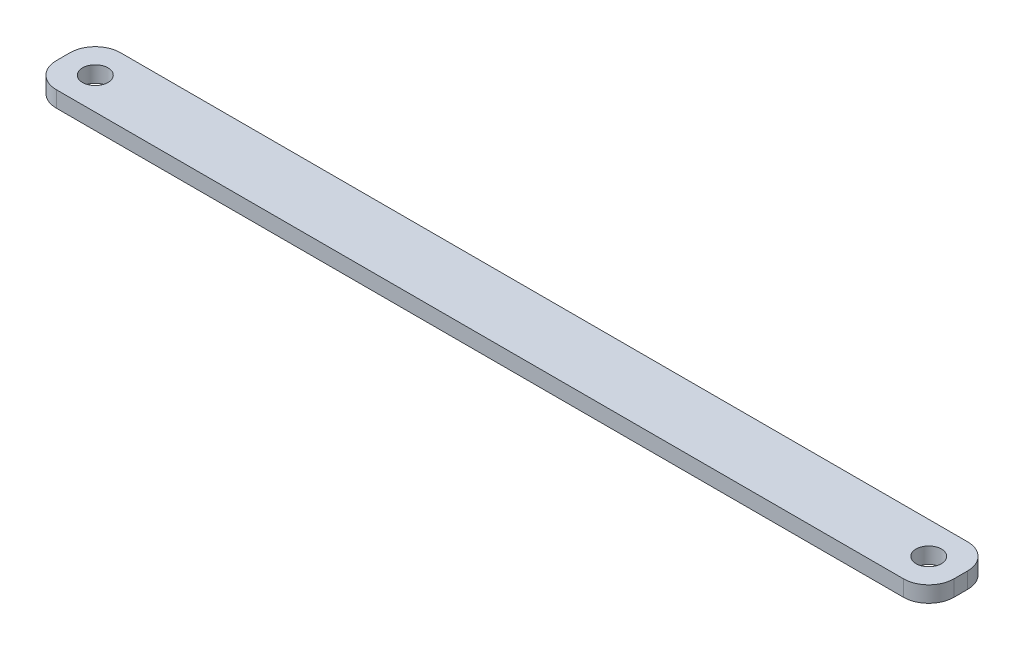
SolidWorks part; units mm, degrees
material "5052-O"
ref_plane "Front Plane" through (0, 0, 0) normal (0, 0, 1) x (1, 0, 0)
ref_plane "Top Plane" through (0, 0, 0) normal (0, 1, 0) x (1, 0, 0)
ref_plane "Right Plane" through (0, 0, 0) normal (1, 0, 0) x (0, 0, -1)
sketch "Sketch1" plane through (0, 0, 0) normal (0, 1, 0) x (1, 0, 0)
  line L1 (-177.8, -12.7) -> (177.8, -12.7)
  line L2 (-177.8, -12.7) -> (-177.8, 12.7)
  line L3 (-177.8, 12.7) -> (177.8, 12.7)
  line L4 (177.8, -12.7) -> (177.8, 12.7)
  line L5 (-177.8, -12.7) -> (177.8, 12.7) construction
  line L6 (-177.8, 12.7) -> (177.8, -12.7) construction
  point P0 (0, 0)
  dimension "D1" = 25.4
  dimension "D2" = 355.6
extrude "Boss-Extrude1" add sketch "Sketch1" along normal mid plane 6.35
fillet "Fillet1" radius 10 4 edges at (177.8, 0, -12.7) (177.8, 0, 12.7) (-177.8, 0, -12.7) (-177.8, 0, 12.7)
sketch "Sketch2" plane through (0, 3.175, 0) normal (0, 1, 0) x (1, 0, 0)
  line L0 (0, -36.7292) -> (0, 36.7292) construction
  line L1 (165.1, 0) -> (-165.1, 0) construction
  line L2 (-177.8, 2.7) -> (-177.8, -2.7) construction
  point P10 (0, 0)
  point P11 (0, 0)
  dimension "D1" = 12.7
hole_wizard "3/8 Clearance Hole1" positions "Sketch5" profile "Sketch7" hole size "3/8" standard "ANSI Inch" end condition through all
sketch "Sketch5" plane through (0, 3.175, 0) normal (0, 1, 0) x (1, 0, 0)
  point P0 (165.1, 0)
  point P3 (-165.1, 0)
sketch "Sketch7" plane through (165.1, 3.175, 0) normal (1, 0, 0) x (0, 0, 1)
  line L0 (0, 0) -> (0, 6.35)
  line L1 (0, 6.35) -> (5.0419, 6.35)
  line L2 (5.0419, 6.35) -> (5.0419, 0)
  line L5 (5.0419, 0) -> (0, 0)
  line L11 (0, -6.35) -> (0, 107.95) construction
  dimension "Thru Hole Dia." = 10.0838
  dimension "Thru Hole Depth" = 6.35
sketch "Sketch9" plane through (0, 3.175, 0) normal (0, 1, 0) x (1, 0, 0)
  line L0 (-177.8, 2.7) -> (-177.8, -2.7) construction
  line L1 (-142.875, -6.35) -> (-136.525, -6.35)
  line L2 (-142.875, -6.35) -> (-142.875, -9.525)
  line L3 (-142.875, -9.525) -> (-136.525, -9.525)
  line L4 (-136.525, -6.35) -> (-136.525, -9.525)
  line L5 (-142.875, -6.35) -> (-136.525, -9.525) construction
  line L6 (-142.875, -9.525) -> (-136.525, -6.35) construction
  line L7 (-167.8, -12.7) -> (167.8, -12.7) construction
  point P4 (-139.7, -7.9375)
  dimension "D1" = 3.175
  dimension "D2" = 6.35
  dimension "D3" = 38.1
  dimension "D4" = 3.175
extrude "Cut-Extrude2" [suppressed] cut sketch "Sketch9" against normal through all
fillet "Fillet2" [suppressed] radius 0.635
pattern_linear "LPattern1" [suppressed] count 3 spacing 69.85 of bodies 105
mirror "Mirror1" [suppressed] about plane through (0, 0, 0) normal (1, 0, 0)
